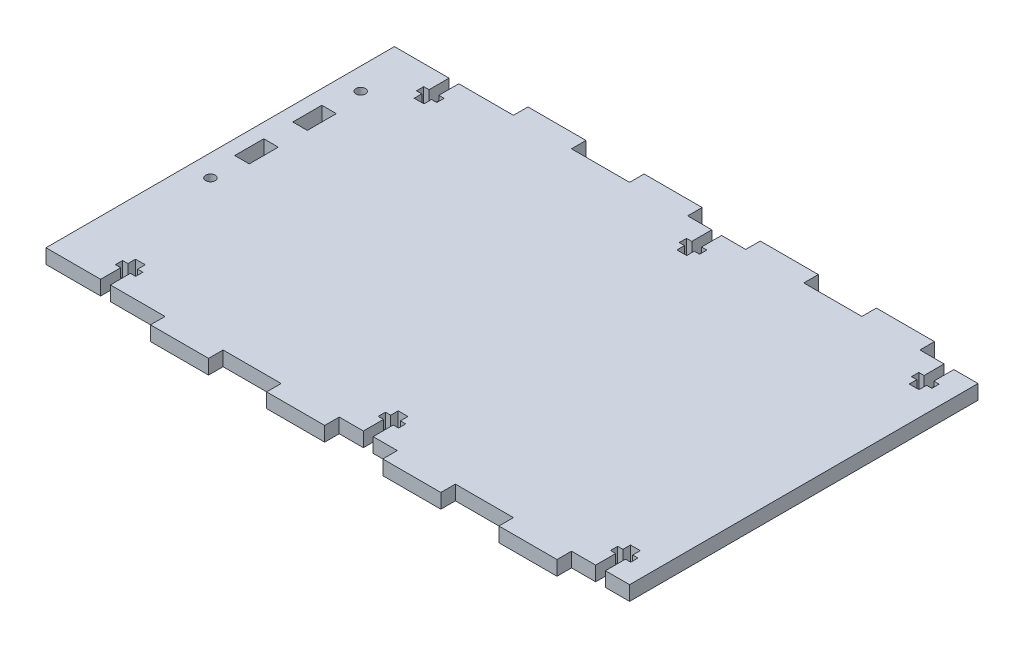
SolidWorks part; units mm, degrees
ref_plane "Front Plane" through (0, 0, 0) normal (0, 0, 1) x (1, 0, 0)
ref_plane "Top Plane" through (0, 0, 0) normal (0, 1, 0) x (1, 0, 0)
ref_plane "Right Plane" through (0, 0, 0) normal (1, 0, 0) x (0, 0, -1)
sketch "Sketch1" plane through (0, 0, 0) normal (0, 0, 1) x (1, 0, 0)
  line L1 (-139.3499, 155.575) -> (115.91, 155.575)
  line L2 (-139.3499, 155.575) -> (-139.3499, 149.225)
  line L3 (-139.3499, 149.225) -> (115.91, 149.225)
  line L4 (115.91, 155.575) -> (115.91, 149.225)
  dimension "D1" = 6.35
extrude "Boss-Extrude1" add sketch "Sketch1" along normal blind 152.4
sketch "Sketch2" plane through (0, 155.575, 0) normal (0, 1, 0) x (1, 0, 0)
  line L0 (90.51, 0) -> (90.51, 6.35)
  line L1 (115.91, 0) -> (-139.3499, 0) construction
  line L2 (-139.3499, 6.35) -> (-87.29, 6.35) construction
  line L3 (90.51, 6.35) -> (65.11, 6.35)
  line L4 (65.11, 6.35) -> (65.11, 0)
  line L5 (115.91, 0) -> (90.51, 0)
  line L6 (90.51, 0) -> (65.11, 0)
  line L9 (115.91, 0) -> (-139.3499, 0)
  line L10 (-139.3499, 0) -> (-139.3499, -152.4)
  line L11 (-139.3499, -152.4) -> (115.91, -152.4)
  line L12 (115.91, -152.4) -> (115.91, 0)
  line L13 (65.11, 0) -> (-139.3499, 0)
  line L14 (-139.3499, 0) -> (-139.3499, -152.4)
  line L15 (-139.3499, -152.4) -> (115.91, -152.4)
  line L16 (115.91, -152.4) -> (115.91, 0)
  line M7 (115.91, 0) -> (-139.3499, 0)
  dimension "D1" = 25.4
  dimension "D2" = 25.4
  dimension "D3" = 0
extrude "Boss-Extrude2" add sketch "Sketch2" against normal blind 6.35 contours L3 L4 L0 M7 region at (77.81, 155.575, -3.175)
pattern_linear "LPattern1" count 4 spacing 50.8 along (-1, 0, 0) of "Boss-Extrude2"
sketch "Sketch3" plane through (0, 0, 152.4) normal (0, 0, 1) x (1, 0, 0)
  line L0 (115.91, 155.575) -> (-139.3499, 155.575) construction
  line L1 (90.51, 155.575) -> (65.11, 155.575)
  line L2 (90.51, 155.575) -> (90.51, 149.225)
  line L3 (90.51, 149.225) -> (65.11, 149.225)
  line L4 (65.11, 155.575) -> (65.11, 149.225)
  line L5 (-139.3499, 149.225) -> (115.91, 149.225) construction
  dimension "D1" = 25.4
  dimension "D2" = 25.4
extrude "Boss-Extrude3" add sketch "Sketch3" along normal blind 6.35
pattern_linear "LPattern2" count 4 spacing 50.8 along (-1, 0, 0) of "Boss-Extrude3"
sketch "Sketch4" plane through (0, 155.575, 0) normal (0, 1, 0) x (1, 0, 0)
  line L0 (-139.3499, 0) -> (-87.29, 0) construction
  line L1 (90.51, 0) -> (115.91, 0) construction
  line L2 (-113.3199, 0) -> (-113.3199, -13.6148) construction
  line L3 (-87.29, 0) -> (-139.3499, 0) construction
  line L4 (1.61, 0) -> (1.61, -16.5479) construction
  line L5 (14.31, 0) -> (-11.09, 0) construction
  line L6 (103.21, 0) -> (103.21, -21.5198) construction
  line L7 (115.91, 0) -> (90.51, 0) construction
  line L8 (103.21, -152.4) -> (103.21, -137.4626) construction
  line L9 (115.91, -152.4) -> (90.51, -152.4) construction
  line L10 (1.61, -152.4) -> (1.61, -137.4626) construction
  line L11 (14.31, -152.4) -> (-11.09, -152.4) construction
  line L12 (-113.3199, -152.4) -> (-113.3199, -137.4626) construction
  line L13 (-87.29, -152.4) -> (-139.3499, -152.4) construction
  line L14 (-139.3499, -152.4) -> (-87.29, -152.4) construction
  line B0 (-111.1863, 0) -> (-115.4535, 0)
  line B1 (-115.4535, -11.938) -> (-117.7649, -11.938)
  line B2 (-117.7649, -11.938) -> (-117.7649, -8.763)
  line B3 (-117.7649, -8.763) -> (-115.4535, -8.763)
  line B4 (-115.4535, -8.763) -> (-115.4535, 0)
  line B5 (-115.4535, -11.938) -> (-115.4535, -15.24)
  line B6 (-115.4535, -15.24) -> (-111.1863, -15.24)
  line B7 (-111.1863, -11.938) -> (-111.1863, -15.24)
  line B8 (-111.1863, -8.763) -> (-111.1863, 0)
  line B9 (-108.8749, -8.763) -> (-111.1863, -8.763)
  line B10 (-108.8749, -11.938) -> (-108.8749, -8.763)
  line B11 (-111.1863, -11.938) -> (-108.8749, -11.938)
  line B12 (3.7436, 0) -> (-0.5236, 0)
  line B13 (-0.5236, -11.938) -> (-2.835, -11.938)
  line B14 (-2.835, -11.938) -> (-2.835, -8.763)
  line B15 (-2.835, -8.763) -> (-0.5236, -8.763)
  line B16 (-0.5236, -8.763) -> (-0.5236, 0)
  line B17 (-0.5236, -11.938) -> (-0.5236, -15.24)
  line B18 (-0.5236, -15.24) -> (3.7436, -15.24)
  line B19 (3.7436, -11.938) -> (3.7436, -15.24)
  line B20 (3.7436, -8.763) -> (3.7436, 0)
  line B21 (6.055, -8.763) -> (3.7436, -8.763)
  line B22 (6.055, -11.938) -> (6.055, -8.763)
  line B23 (3.7436, -11.938) -> (6.055, -11.938)
  line B24 (105.3436, 0) -> (101.0764, 0)
  line B25 (101.0764, -11.938) -> (98.765, -11.938)
  line B26 (98.765, -11.938) -> (98.765, -8.763)
  line B27 (98.765, -8.763) -> (101.0764, -8.763)
  line B28 (101.0764, -8.763) -> (101.0764, 0)
  line B29 (101.0764, -11.938) -> (101.0764, -15.24)
  line B30 (101.0764, -15.24) -> (105.3436, -15.24)
  line B31 (105.3436, -11.938) -> (105.3436, -15.24)
  line B32 (105.3436, -8.763) -> (105.3436, 0)
  line B33 (107.655, -8.763) -> (105.3436, -8.763)
  line B34 (107.655, -11.938) -> (107.655, -8.763)
  line B35 (105.3436, -11.938) -> (107.655, -11.938)
  line B36 (-115.4535, -152.4) -> (-111.1863, -152.4)
  line B37 (-111.1863, -140.462) -> (-108.8749, -140.462)
  line B38 (-108.8749, -140.462) -> (-108.8749, -143.637)
  line B39 (-108.8749, -143.637) -> (-111.1863, -143.637)
  line B40 (-111.1863, -143.637) -> (-111.1863, -152.4)
  line B41 (-111.1863, -140.462) -> (-111.1863, -137.16)
  line B42 (-111.1863, -137.16) -> (-115.4535, -137.16)
  line B43 (-115.4535, -140.462) -> (-115.4535, -137.16)
  line B44 (-115.4535, -143.637) -> (-115.4535, -152.4)
  line B45 (-117.7649, -143.637) -> (-115.4535, -143.637)
  line B46 (-117.7649, -140.462) -> (-117.7649, -143.637)
  line B47 (-115.4535, -140.462) -> (-117.7649, -140.462)
  line B48 (-0.5236, -152.4) -> (3.7436, -152.4)
  line B49 (3.7436, -140.462) -> (6.055, -140.462)
  line B50 (6.055, -140.462) -> (6.055, -143.637)
  line B51 (6.055, -143.637) -> (3.7436, -143.637)
  line B52 (3.7436, -143.637) -> (3.7436, -152.4)
  line B53 (3.7436, -140.462) -> (3.7436, -137.16)
  line B54 (3.7436, -137.16) -> (-0.5236, -137.16)
  line B55 (-0.5236, -140.462) -> (-0.5236, -137.16)
  line B56 (-0.5236, -143.637) -> (-0.5236, -152.4)
  line B57 (-2.835, -143.637) -> (-0.5236, -143.637)
  line B58 (-2.835, -140.462) -> (-2.835, -143.637)
  line B59 (-0.5236, -140.462) -> (-2.835, -140.462)
  line B60 (101.0764, -152.4) -> (105.3436, -152.4)
  line B61 (105.3436, -140.462) -> (107.655, -140.462)
  line B62 (107.655, -140.462) -> (107.655, -143.637)
  line B63 (107.655, -143.637) -> (105.3436, -143.637)
  line B64 (105.3436, -143.637) -> (105.3436, -152.4)
  line B65 (105.3436, -140.462) -> (105.3436, -137.16)
  line B66 (105.3436, -137.16) -> (101.0764, -137.16)
  line B67 (101.0764, -140.462) -> (101.0764, -137.16)
  line B68 (101.0764, -143.637) -> (101.0764, -152.4)
  line B69 (98.765, -143.637) -> (101.0764, -143.637)
  line B70 (98.765, -140.462) -> (98.765, -143.637)
  line B71 (101.0764, -140.462) -> (98.765, -140.462)
sketch_block_instance "TSlot-1"
sketch_block "TSlot" parameters "D1"=3.302, "D2"=3.175
sketch_block_instance "TSlot-3"
sketch_block_instance "TSlot-4"
sketch_block_instance "TSlot-9"
sketch_block_instance "TSlot-11"
sketch_block_instance "TSlot-12"
extrude "Cut-Extrude1" cut sketch "Sketch4" against normal blind 6.35
sketch "Sketch5" plane through (0, 155.575, 0) normal (0, 1, 0) x (1, 0, 0)
  line L0 (-132.9999, -55.2358) -> (-132.9999, -140.7347) construction
  line L1 (-132.9999, -38.1) -> (-126.6499, -38.1)
  line L2 (-132.9999, -38.1) -> (-132.9999, -50.8)
  line L3 (-132.9999, -50.8) -> (-126.6499, -50.8)
  line L4 (-126.6499, -38.1) -> (-126.6499, -50.8)
  line L5 (-132.9999, -63.5) -> (-126.6499, -63.5)
  line L6 (-132.9999, -63.5) -> (-132.9999, -76.2)
  line L7 (-132.9999, -76.2) -> (-126.6499, -76.2)
  line L8 (-126.6499, -63.5) -> (-126.6499, -76.2)
  line L10 (-139.3499, -152.4) -> (-139.3499, 0) construction
  line L11 (-115.4535, 0) -> (-139.3499, 0) construction
  dimension "D1" = 12.7
  dimension "D2" = 6.35
  dimension "D3" = 6.35
  dimension "D4" = 12.7
  dimension "D5" = 12.7
  dimension "D6" = 6.35
  dimension "D7" = 38.1
extrude "Cut-Extrude2" cut sketch "Sketch5" against normal through all
sketch "Sketch6" plane through (0, 155.575, 0) normal (0, 1, 0) x (1, 0, 0)
  line L0 (-132.9999, -22.1864) -> (-126.6499, -26.4536) construction
  line L1 (-132.9999, -26.4536) -> (-126.6499, -22.1864) construction
  line L2 (-132.9999, -87.8464) -> (-126.6499, -92.1136) construction
  line L3 (-132.9999, -92.1136) -> (-126.6499, -87.8464) construction
  circle A0 centre (-129.8249, -89.98) radius 2.0955
  circle A1 centre (-129.8249, -24.32) radius 2.0955
  dimension "D1" = 4.191
extrude "Cut-Extrude3" cut sketch "Sketch6" against normal through all
